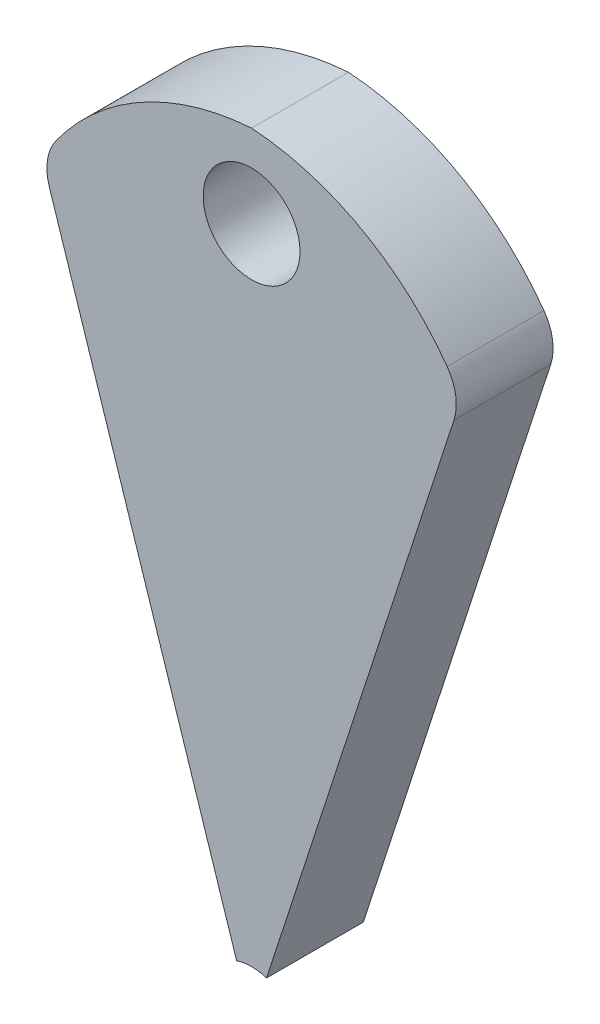
SolidWorks part; units mm, degrees
ref_plane "Front" through (0, 0, 0) normal (0, 0, 1) x (1, 0, 0)
ref_plane "Top" through (0, 0, 0) normal (0, 1, 0) x (1, 0, 0)
ref_plane "Right" through (0, 0, 0) normal (1, 0, 0) x (0, 0, -1)
sketch "Sketch1" plane through (0, 0, 0) normal (0, 0, 1) x (1, 0, 0)
  line L0 (0, 0) -> (0, 800) construction
  line L1 (15.4508, 47.5528) -> (208.9633, 643.123)
  line L2 (-15.4508, 47.5528) -> (-208.9633, 643.123)
  circle A0 centre (0, 0) radius 800 construction
  circle A11 centre (0, 0) radius 50 construction
  circle A14 centre (0, 714.39) radius 50
  arc A16 (-201.9687, 687.8148) -> (0, 800) centre (18.4378, 528.91) cw
  arc A17 (201.9687, 687.8148) -> (0, 800) centre (-18.4378, 528.91) ccw
  arc A18 (201.9687, 687.8148) -> (208.9633, 643.123) centre (161.4105, 658.5738) cw
  arc A19 (-201.9687, 687.8148) -> (-208.9633, 643.123) centre (-161.4105, 658.5738) ccw
  arc A20 (15.4508, 47.5528) -> (-15.4508, 47.5528) centre (0, 0) ccw
  point P15 (216.3119, 665.7396)
  point P18 (-216.3119, 665.7396)
  dimension "D1" = 1600
  dimension "D2" = 100
  dimension "D4" = 714.39
  dimension "D5" = 50
  dimension "D6" = 100
  dimension "D3" = 36
extrude "Boss-Extrude1" add sketch "Sketch1" along normal blind 100
sketch "Sketch3" plane through (0, 0, 0) normal (0, 0, 1) x (1, 0, 0)
  circle A1 centre (0, 0) radius 630 construction
  circle A4 centre (0, 630) radius 15
  dimension "D1" = 30
  dimension "D3" = 1260
extrude "Boss-Extrude2" add sketch "Sketch3" against normal blind 100
sketch "Sketch4" plane through (0, 0, 0) normal (0, 0, 1) x (1, 0, 0)
  line L0 (0, 0) -> (0, 883.6773) construction
ref_axis "Axis2" through (0, 0, 0) along (0, 1, 0)
scale "Echelle1" bodies to scale 117 scale about centroid uniform scaling yes scale factor 0.075
